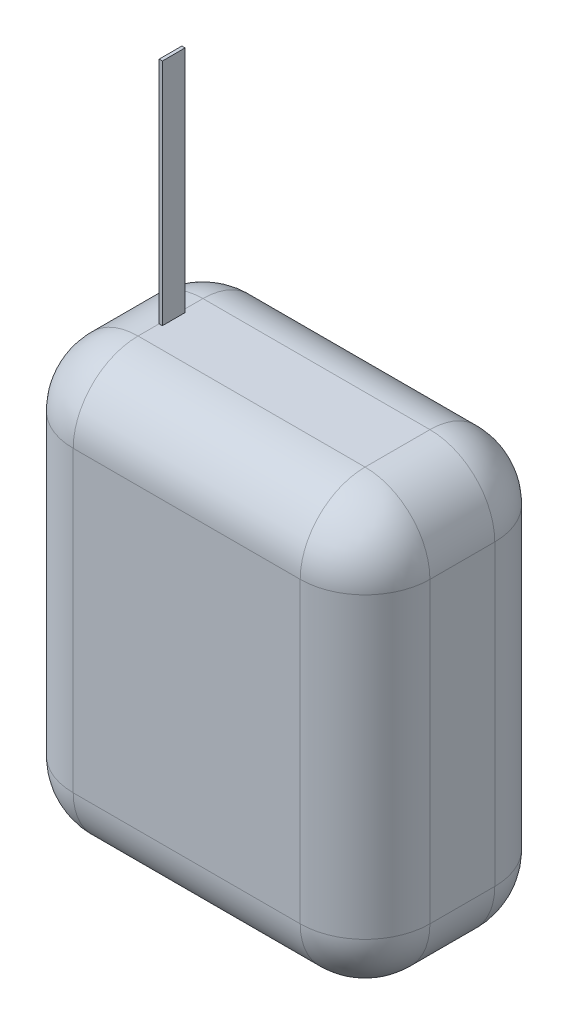
SolidWorks part; units mm, degrees
ref_plane "前视基准面" through (0, 0, 0) normal (0, 0, 1) x (1, 0, 0)
ref_plane "上视基准面" through (0, 0, 0) normal (0, 1, 0) x (1, 0, 0)
ref_plane "右视基准面" through (0, 0, 0) normal (1, 0, 0) x (0, 0, -1)
sketch "草图1" plane through (0, 0, 0) normal (0, 0, 1) x (1, 0, 0)
  line L1 (-27.5, 33) -> (27.5, 33)
  line L2 (-27.5, 33) -> (-27.5, -33)
  line L3 (-27.5, -33) -> (27.5, -33)
  line L4 (27.5, 33) -> (27.5, -33)
  line L5 (-27.5, 33) -> (27.5, -33) construction
  line L6 (-27.5, -33) -> (27.5, 33) construction
  point P0 (0, 0)
extrude "凸台-拉伸1" add sketch "草图1" along normal blind 30
fillet "圆角1" radius 10 12 edges at (27.5, 0, 30) (0, -33, 30) (27.5, -33, 15) (0, -33, 0) (27.5, 0, 0) (-27.5, 0, 30) (-27.5, -33, 15) (-27.5, 0, 0) (27.5, 33, 15) (0, 33, 30) (-27.5, 33, 15) (0, 33, 0)
ref_plane "基准面4" through (-17.5, 0, 0) normal (-1, 0, 0) x (0, 0, 1)
sketch "草图2" plane through (-17.5, 0, 0) normal (-1, 0, 0) x (0, 0, 1)
  line L0 (10, 33) -> (20, 33)
  line L1 (14.75, 33) -> (15.25, 33)
  line L2 (14.75, 33) -> (14.75, 68.3506)
  line L3 (14.75, 68.3506) -> (15.25, 68.3506)
  line L4 (15.25, 33) -> (15.25, 68.3506)
  line L5 (10, 33) -> (20, 33) construction
  line L6 (15.25, 33) -> (15.75, 33)
  line L7 (15.25, 33) -> (15.25, 68.3506)
  line L8 (15.25, 68.3506) -> (15.75, 68.3506)
  line L9 (15.75, 33) -> (15.75, 68.3506)
  line L10 (15.75, 33) -> (16.25, 33)
  line L11 (15.75, 33) -> (15.75, 68.3506)
  line L12 (15.75, 68.3506) -> (16.25, 68.3506)
  line L13 (16.25, 33) -> (16.25, 68.3506)
  line L14 (16.25, 33) -> (16.75, 33)
  line L15 (16.25, 33) -> (16.25, 68.3506)
  line L16 (16.25, 68.3506) -> (16.75, 68.3506)
  line L17 (16.75, 33) -> (16.75, 68.3506)
  line L18 (14.25, 33) -> (14.75, 33)
  line L19 (14.25, 33) -> (14.25, 68.3506)
  line L20 (14.25, 68.3506) -> (14.75, 68.3506)
  line L21 (14.75, 33) -> (14.75, 68.3506)
  line L22 (13.75, 33) -> (14.25, 33)
  line L23 (13.75, 33) -> (13.75, 68.3506)
  line L24 (13.75, 68.3506) -> (14.25, 68.3506)
  line L25 (14.25, 33) -> (14.25, 68.3506)
  line L26 (13.25, 33) -> (13.75, 33)
  line L27 (13.25, 33) -> (13.25, 68.3506)
  line L28 (13.25, 68.3506) -> (13.75, 68.3506)
  line L29 (13.75, 33) -> (13.75, 68.3506)
  arc A0 (10, 33) -> (0, 23) centre (10, 23) ccw construction
  point P5 (15, 33)
  point P16 (15.25, 33)
  point P19 (15.5, 33)
  point P20 (15.75, 33)
  point P25 (16, 33)
  point P26 (16.25, 33)
  point P31 (16.5, 33)
  point P32 (16.75, 33)
  point P37 (14.5, 33)
  point P38 (14.75, 33)
  point P43 (14, 33)
  point P44 (14.25, 33)
  point P49 (13.5, 33)
  point P50 (13.75, 33)
  dimension "D1" = 4
  dimension "D2" = 4
extrude "凸台-拉伸2" add sketch "草图2" against normal blind 0.5 contours L28 L27 L0 L23 region at (-17.5, 50.6753, 13.5)
extrude "凸台-拉伸4" add sketch "草图2<4>" against normal blind 0.5 contours L23 L24 L25 L22
sketch "草图2<4>" plane through (-17.5, 0, 0) normal (-1, 0, 0) x (0, 0, 1) same geometry as "草图2"
extrude "凸台-拉伸5" add sketch "草图2<5>" against normal blind 0.5 contours L2 L3 L4 L1
sketch "草图2<5>" plane through (-17.5, 0, 0) normal (-1, 0, 0) x (0, 0, 1) same geometry as "草图2"
extrude "凸台-拉伸6" add sketch "草图2<6>" against normal blind 0.5 contours L20 L21 L18 L19
sketch "草图2<6>" plane through (-17.5, 0, 0) normal (-1, 0, 0) x (0, 0, 1) same geometry as "草图2"
extrude "凸台-拉伸7" add sketch "草图2<7>" against normal blind 0.5 contours L0 L13 L12 L9 | L0 L17 L16 L13 | L8 L9 L6 L7 region at (-17.5, 50.6753, 16) region at (-17.5, 50.6753, 16.5)
sketch "草图2<7>" plane through (-17.5, 0, 0) normal (-1, 0, 0) x (0, 0, 1) same geometry as "草图2"
